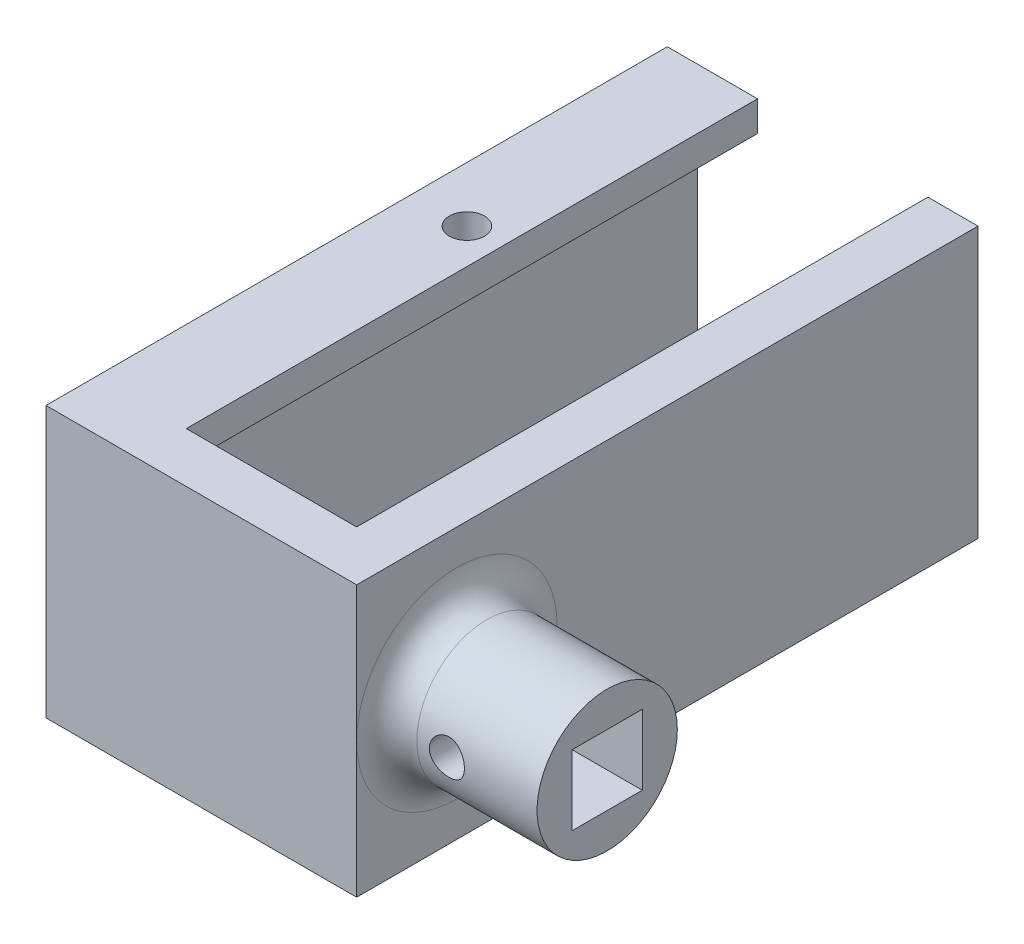
SolidWorks part; units mm, degrees
ref_plane "Plan de face" through (0, 0, 0) normal (1, 0, 0) x (0, 1, 0)
ref_plane "Plan de dessus" through (0, 0, 0) normal (0, 0, 1) x (0, 1, 0)
ref_plane "Plan de droite" through (0, 0, 0) normal (0, 1, 0) x (-1, 0, 0)
sketch "Esquisse1" plane through (0, 0, 0) normal (1, 0, 0) x (0, 1, 0)
  line L1 (-13.5, 31) -> (13.5, 31)
  line L2 (-13.5, 31) -> (-13.5, -31)
  line L3 (-13.5, -31) -> (13.5, -31)
  line L4 (13.5, 31) -> (13.5, -31)
  line L5 (-13.5, 31) -> (13.5, -31) construction
  line L6 (-13.5, -31) -> (13.5, 31) construction
  point P0 (0, 0)
  dimension "D1" = 27
  dimension "D2" = 62
extrude "Boss.-Extru.1" add sketch "Esquisse1" along normal blind 3
sketch "Esquisse2" plane through (3, 0, 0) normal (1, 0, 0) x (0, 1, 0)
  line L0 (-13.5, 31) -> (-10.5, 31)
  line L1 (13.5, 31) -> (-13.5, 31) construction
  line L2 (-10.5, 31) -> (-10.5, -31)
  line L3 (-13.5, -31) -> (13.5, -31) construction
  line L4 (-10.5, -31) -> (-13.5, -31)
  line L5 (-13.5, -31) -> (-13.5, 31)
  line L6 (-13.5, 26) -> (-10.5, 26)
  line L7 (-13.5, -26) -> (-10.5, -26)
  line M8 (13.5, 31) -> (-13.5, 31)
  line M9 (-13.5, 31) -> (-13.5, -31)
  line M10 (-13.5, -31) -> (13.5, -31)
  dimension "D1" = 3
  dimension "D2" = 5
  dimension "D3" = 5
extrude "Boss.-Extru.2" add sketch "Esquisse2" along normal blind 6 contours L5 L7 L2 L6 region at (3, -12, 0)
extrude "Boss.-Extru.3" add sketch "Esquisse2<3>" along normal blind 28 contours L6 L2 M9 M8 | L7 L2 M9 M10 region at (3, -12, 28.5) region at (3, -12, -28.5)
sketch "Esquisse2<3>" plane through (3, 0, 0) normal (1, 0, 0) x (0, 1, 0) same geometry as "Esquisse2"
extrude "Boss.-Extru.4" add sketch "Esquisse2<4>" along normal blind 5 from offset 23 contours L5 L7 L2 L6 region at (3, -12, 0)
sketch "Esquisse2<4>" plane through (3, 0, 0) normal (1, 0, 0) x (0, 1, 0) same geometry as "Esquisse2"
mirror "Symétrie1" about plane through (0, 0, 0) normal (0, 1, 0) of "Boss.-Extru.2", "Boss.-Extru.3", "Boss.-Extru.4"
sketch "Esquisse3" plane through (3, 0, 0) normal (1, 0, 0) x (0, 1, 0)
  line L0 (-10.5, 31) -> (-10.5, 26)
  line L1 (-10.5, 31) -> (-10.5, -31) construction
  line L2 (-10.5, 26) -> (10.5, 26)
  line L3 (10.5, 31) -> (10.5, -31) construction
  line L4 (10.5, 26) -> (10.5, 31)
  line L5 (10.5, 31) -> (-10.5, 31)
  dimension "D1" = 5
extrude "Boss.-Extru.5" add sketch "Esquisse3" along normal blind 28
sketch "Esquisse4" plane through (0, 0, 26) normal (0, 0, -1) x (-1, 0, 0)
  line L2 (-31, 10.5) -> (-31, -10.5)
  line L5 (-31, -10.5) -> (-31, 10.5) construction
  line L6 (-31, 10.5) -> (-26, 10.5)
  line L7 (-31, 10.5) -> (-26, 10.5) construction
  line L8 (-26, 10.5) -> (-26, -10.5)
  line L9 (-31, -10.5) -> (-3, -10.5) construction
  line L10 (-26, -10.5) -> (-31, -10.5)
  dimension "D1" = 5
extrude "Boss.-Extru.6" add sketch "Esquisse4" along normal blind 57
sketch "Esquisse5" plane through (31, 0, 0) normal (1, 0, 0) x (0, 1, 0)
  line L1 (-3.5, 24.5) -> (3.5, 24.5)
  line L2 (-3.5, 24.5) -> (-3.5, 17.5)
  line L3 (-3.5, 17.5) -> (3.5, 17.5)
  line L4 (3.5, 24.5) -> (3.5, 17.5)
  line L5 (-3.5, 24.5) -> (3.5, 17.5) construction
  line L6 (-3.5, 17.5) -> (3.5, 24.5) construction
  line L7 (0, 0) -> (0, -6.407) construction
  line L8 (13.5, 31) -> (-13.5, 31) construction
  circle A0 centre (0, 21) radius 7
  dimension "D3" = 14
  dimension "D1" = 7
  dimension "D2" = 7
  dimension "D4" = 10
extrude "Boss.-Extru.7" add sketch "Esquisse5" along normal blind 15
fillet "Congé1" radius 3 1 edges at (31, 0, 14)
sketch "Esquisse7" plane through (0, 13.5, 0) normal (0, 1, 0) x (1, 0, 0)
  line L0 (31, 31) -> (0, 31) construction
  line L1 (26, 26) -> (9, 26)
  line L2 (26, 26) -> (26, 31)
  line L3 (26, 31) -> (9, 31)
  line L4 (9, 26) -> (9, 31)
  line L5 (9, -26) -> (9, 26) construction
extrude "Enlèv. mat.-Extru.1" cut sketch "Esquisse7" against normal through all
sketch "Esquisse8" plane through (0, -13.5, 0) normal (0, -1, 0) x (1, 0, 0)
  line L0 (0, 31) -> (0, -31) construction
  line L1 (31, 31) -> (0, 31) construction
  circle A0 centre (5.5, -5.5) radius 1.75
  dimension "D1" = 3.5
  dimension "D2" = 5.5
  dimension "D3" = 36.5
extrude "Enlèv. mat.-Extru.2" cut sketch "Esquisse8" against normal through all
sketch "Esquisse9" plane through (0, -13.5, 0) normal (0, -1, 0) x (1, 0, 0)
  circle A0 centre (5.5, -5.5) radius 3
  dimension "D1" = 6
extrude "Enlèv. mat.-Extru.5" cut sketch "Esquisse9" against normal blind 1.5
sketch "Esquisse10" plane through (0, 0, 17.5) normal (0, 0, 1) x (1, 0, 0)
  line L0 (31, -10) -> (31, 10) construction
  line L1 (0, 0) -> (-2.0131, 0) construction
  circle A0 centre (37, 0) radius 1.75
  dimension "D1" = 3.5
  dimension "D2" = 6
extrude "Enlèv. mat.-Extru.6" cut sketch "Esquisse10" against normal through all and the other way through all
